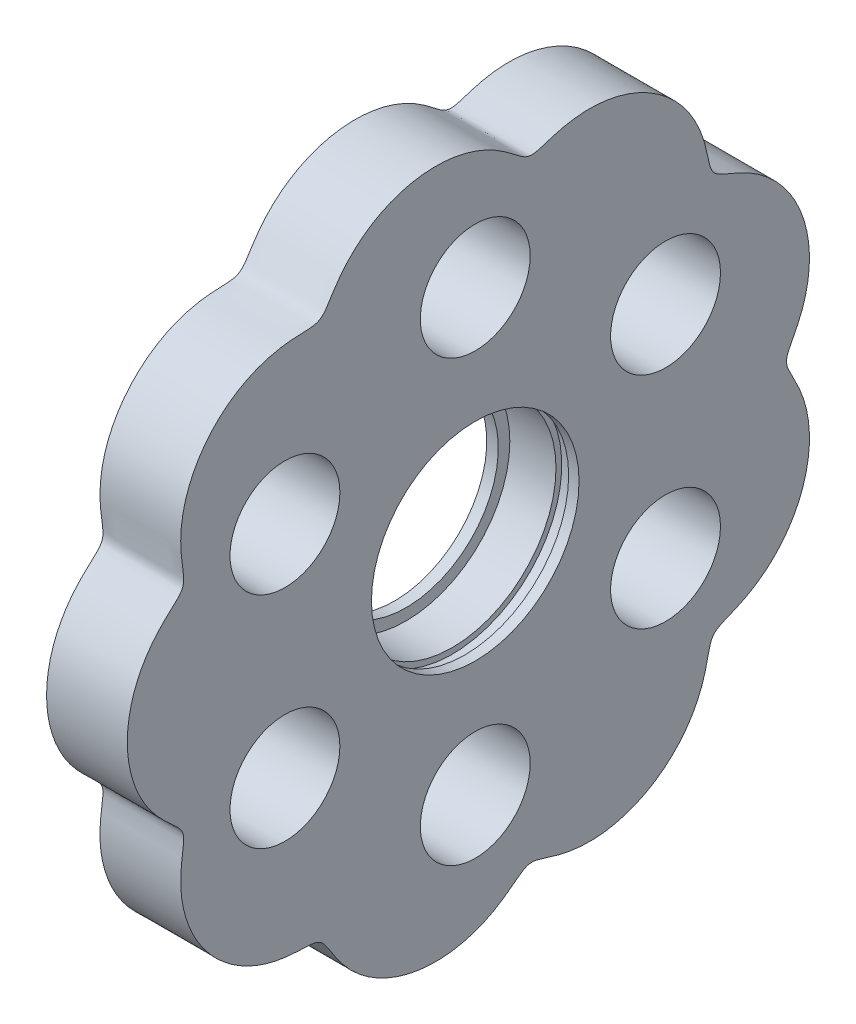
SolidWorks part; units mm, degrees
ref_plane "Front Plane" through (0, 0, 0) normal (0, 0, 1) x (1, 0, 0)
ref_plane "Top Plane" through (0, 0, 0) normal (0, 1, 0) x (1, 0, 0)
ref_plane "Right Plane" through (0, 0, 0) normal (1, 0, 0) x (0, 0, -1)
sketch "Sketch1" plane through (0, 0, 0) normal (1, 0, 0) x (0, 0, -1)
  circle A0 centre (0, 0) radius 9
  circle A1 centre (0, 0) radius 19.05 construction
  circle A2 centre (0, 19.05) radius 4.7625
  circle A3 centre (16.4978, 9.525) radius 4.7625
  circle A4 centre (16.4978, -9.525) radius 4.7625
  circle A5 centre (0, -19.05) radius 4.7625
  circle A6 centre (-16.4978, -9.525) radius 4.7625
  circle A7 centre (-16.4978, 9.525) radius 4.7625
  arc A8 (26.9875, 0) -> (26.994, 0.1287) centre (28.2671, 0) cw
  spline S0 degree 4 poles (24.0888, 15.5706) (24.4053, 15.3745) (25.0197, 14.9519) (25.8769, 14.2292) (26.8672, 13.1095) (27.6864, 11.8592) (28.3198, 10.5054) (28.7555, 9.0756) (28.9842, 7.5985) (28.9992, 6.1037) (28.7969, 4.6225) (28.4319, 3.3662) (27.9939, 2.3365) (27.6319, 1.6364) (27.4151, 1.2322) (27.2721, 0.9508) (27.1976, 0.7951) (27.1297, 0.6399) (27.0713, 0.4845) (27.0322, 0.3515) (27.009, 0.2424) (26.9965, 0.158) (26.9903, 0.0923) (26.9872, 0.0214) (26.9873, -0.0243) (26.9907, -0.0988) (26.9976, -0.1672) (27.0116, -0.2569) (27.033, -0.3527) (27.0616, -0.4505) (27.0986, -0.5565) (27.1336, -0.6462) (27.184, -0.7644) (27.252, -0.9101) (27.336, -1.0777) (27.4557, -1.3071) (27.5979, -1.5747) (27.8035, -1.97) (28.1452, -2.6757) (28.5405, -3.6809) (28.8775, -5.0165) (29.0228, -6.5839) (28.9282, -8.155) (28.602, -9.681) (28.0595, -11.1296) (27.3186, -12.4723) (26.3986, -13.6824) (25.3108, -14.7449) (24.0763, -15.6324) (22.9569, -16.2115) (22.0305, -16.5814) (21.3839, -16.8484) (21.04, -17.024) (20.7809, -17.218) (20.5918, -17.4348) (20.4481, -17.6972) (20.3419, -18.0072) (20.2297, -18.4621) (20.1126, -19.0338) (19.914, -19.899) (19.5509, -21.0362) (18.9588, -22.3) (18.0652, -23.6211) (16.9786, -24.7884) (15.741, -25.7664) (14.387, -26.5407) (12.9504, -27.1023) (11.4642, -27.4448) (9.9433, -27.5649) (8.4218, -27.4553) (7.1873, -27.1813) (6.2364, -26.8693) (5.5675, -26.6566) (5.1904, -26.5681) (4.8658, -26.547) (4.5781, -26.5886) (4.2474, -26.7152) (3.8366, -26.9833) (3.3422, -27.3762) (2.7495, -27.8328) (2.0842, -28.286) (1.2132, -28.7906) (0.1095, -29.2852) (-1.2457, -29.6877) (-2.8471, -29.9) (-4.4265, -29.864) (-5.9478, -29.6003) (-7.3813, -29.1318) (-8.7031, -28.4822) (-9.9193, -27.651) (-10.8676, -26.778) (-11.5836, -25.939) (-12.0909, -25.227) (-12.44, -24.6828) (-12.7368, -24.2034) (-12.9824, -23.8371) (-13.2161, -23.5701) (-13.4342, -23.3978) (-13.6702, -23.2745) (-14.0009, -23.1817) (-14.4257, -23.1396) (-14.975, -23.12) (-15.6229, -23.0959) (-16.5059, -23.0244) (-17.6152, -22.8368) (-18.8754, -22.461) (-20.2365, -21.8245) (-21.4907, -20.9972) (-22.6347, -19.9799) (-23.6367, -18.7847) (-24.4641, -17.4286) (-25.0837, -15.9347) (-25.4617, -14.3623) (-25.5708, -12.9509) (-25.5065, -11.7424) (-25.3804, -10.8005) (-25.2874, -10.175) (-25.2596, -9.6848) (-25.3141, -9.3347) (-25.4207, -9.0643) (-25.6003, -8.7933) (-25.8648, -8.5109) (-26.3827, -8.0382) (-27.1277, -7.3718) (-27.982, -6.4414) (-28.838, -5.1809) (-29.4952, -3.8061) (-29.9431, -2.3501) (-30.1773, -0.8262) (-30.1859, 0.7334) (-29.9601, 2.2957) (-29.4936, 3.8223) (-28.7978, 5.2598) (-27.8844, 6.5692) (-26.9944, 7.5041) (-26.2533, 8.1483) (-25.7691, 8.6082) (-25.554, 8.8559) (-25.397, 9.1107) (-25.3029, 9.3826) (-25.2632, 9.7035) (-25.2825, 10.0889) (-25.374, 10.7816) (-25.5173, 11.7677) (-25.5763, 13.0252) (-25.4267, 14.5364) (-25.0526, 16.0084) (-24.4671, 17.4093) (-23.6805, 18.7173) (-22.7082, 19.9035) (-21.5677, 20.9412) (-20.2801, 21.8031) (-18.8777, 22.4636) (-17.3913, 22.9024) (-16.1126, 23.0797) (-15.0844, 23.1155) (-14.3595, 23.1435) (-13.9557, 23.1908) (-13.6345, 23.2884) (-13.3798, 23.4308) (-13.1556, 23.6314) (-12.9492, 23.8869) (-12.5804, 24.4445) (-12.0739, 25.2868) (-11.3064, 26.3262) (-10.1733, 27.4532) (-8.8763, 28.3877) (-7.4517, 29.1112) (-5.951, 29.6032) (-4.4132, 29.8635) (-2.8725, 29.8956) (-1.3626, 29.7057) (0.1036, 29.2961) (1.4916, 28.6715) (2.5547, 27.9917) (3.3393, 27.3739) (3.8944, 26.9467) (4.2184, 26.7359) (4.5167, 26.6071) (4.8017, 26.5501) (5.1561, 26.5584) (5.6344, 26.6716) (6.2346, 26.8723) (6.9494, 27.0987) (7.7315, 27.2964) (8.7249, 27.4714) (9.934, 27.5567) (11.3479, 27.4681) (12.9278, 27.1153) (14.407, 26.5337) (15.757, 25.7527) (16.9557, 24.8017) (17.986, 23.7101) (18.847, 22.4805) (19.4343, 21.3054) (19.8105, 20.2463) (20.0336, 19.3898) (20.1695, 18.7566) (20.2843, 18.2196) (20.3998, 17.809) (20.5517, 17.4956) (20.7345, 17.262) (21.0076, 17.0389) (21.4443, 16.8166) (22.0311, 16.585) (22.7222, 16.3006) (23.4467, 15.952) (24.3186, 15.4512) (25.2985, 14.7445) (26.3245, 13.7743) (27.3096, 12.4964) (28.0876, 11.08) (28.6409, 9.5587) (28.9552, 7.968) (29.0115, 6.5478) (28.8998, 5.3367) (28.7005, 4.3444) (28.5064, 3.663) (28.3024, 3.0913) (28.0706, 2.5305) (27.8776, 2.1183) (27.6938, 1.758) (27.5289, 1.445) (27.4344, 1.2661) (27.3474, 1.0997) (27.2692, 0.9445) (27.2006, 0.8008) (27.1419, 0.6679) (27.0943, 0.547) (27.0609, 0.4471) (27.0392, 0.3712) (27.0263, 0.32) (27.0169, 0.2778) (27.0063, 0.2221) (26.9958, 0.1509) (26.991, 0.1035) (26.9863, 0.0082) (26.9882, -0.0616) (26.9948, -0.1466) (27.0074, -0.2355) (27.0276, -0.33) (27.0557, -0.4305) (27.0857, -0.521) (27.1377, -0.6595) (27.2184, -0.8429) (27.3309, -1.0692) (27.4729, -1.3393) (27.6704, -1.7121) (27.9155, -2.1918) (28.1879, -2.7884) (28.4595, -3.5119) (28.7312, -4.4391) (28.9435, -5.5805) (29.0209, -6.9348) (28.8774, -8.4783) (28.5081, -9.9836) (27.9223, -11.4186) (27.1321, -12.7521) (26.1529, -13.9539) (25.2912, -14.7345) (24.6685, -15.1927) (24.3465, -15.4056) knots 0 0 0 0 0 0.006514 0.01303 0.019546 0.026062 0.032577 0.039093 0.045609 0.052125 0.05864 0.065156 0.068414 0.071671 0.072426 0.073181 0.073936 0.074691 0.075388 0.076084 0.076359 0.076634 0.076909 0.077183 0.077474 0.077765 0.078056 0.078347 0.079094 0.079468 0.079841 0.08031 0.080779 0.081716 0.082653 0.08359 0.085305 0.087019 0.090448 0.097307 0.104164 0.111022 0.11788 0.124738 0.131364 0.137989 0.144616 0.151241 0.157866 0.164493 0.16659 0.168688 0.17011 0.171229 0.172221 0.173681 0.175312 0.176944 0.180417 0.183891 0.190839 0.197787 0.204734 0.211683 0.218631 0.225278 0.231925 0.238574 0.245221 0.251867 0.258517 0.260621 0.262725 0.264152 0.265274 0.266279 0.267774 0.270299 0.273819 0.277338 0.280856 0.284374 0.291412 0.298448 0.305486 0.312523 0.318944 0.325364 0.331785 0.338206 0.344627 0.347837 0.351047 0.353492 0.355937 0.357703 0.358757 0.359673 0.360776 0.362332 0.364727 0.367122 0.370397 0.373672 0.38022 0.386769 0.393319 0.399867 0.406416 0.413461 0.420507 0.427551 0.434596 0.441641 0.445164 0.448688 0.451216 0.452712 0.453718 0.454839 0.456265 0.458367 0.460468 0.46711 0.473749 0.480388 0.487029 0.493669 0.500309 0.507265 0.514221 0.521176 0.528131 0.535088 0.542043 0.543676 0.545309 0.546771 0.547764 0.548881 0.550302 0.552397 0.554492 0.561111 0.567729 0.574346 0.580965 0.587583 0.594201 0.600954 0.607708 0.614461 0.621213 0.627968 0.634721 0.636963 0.639205 0.640666 0.641809 0.642803 0.644267 0.645902 0.647536 0.654498 0.661461 0.668423 0.675385 0.682348 0.689311 0.695944 0.702577 0.709212 0.715844 0.722477 0.729112 0.731211 0.733311 0.734735 0.735855 0.736862 0.73836 0.740891 0.744417 0.747944 0.75147 0.754996 0.762047 0.769099 0.776151 0.783204 0.789746 0.796288 0.802831 0.809373 0.815915 0.819187 0.822458 0.824851 0.827244 0.828799 0.8299 0.830904 0.832398 0.83492 0.838435 0.84195 0.845465 0.848979 0.856009 0.863037 0.870067 0.877096 0.884172 0.891248 0.898323 0.901861 0.905399 0.908937 0.910706 0.912475 0.916013 0.916897 0.917782 0.918666 0.919551 0.920185 0.92082 0.921454 0.922089 0.922464 0.922652 0.92284 0.923028 0.923216 0.923591 0.923945 0.924298 0.924584 0.92487 0.925442 0.925859 0.926276 0.926694 0.927111 0.928446 0.92978 0.931115 0.93245 0.935827 0.939204 0.942582 0.945959 0.952715 0.95947 0.966225 0.97298 0.979735 0.986491 0.993246 1 1 1 1 1 construction
  spline S1 degree 4 poles (26.9875, 0) (26.9875, -0.0141) (26.9881, -0.0422) (26.9907, -0.0988) (26.9976, -0.1672) (27.0116, -0.2569) (27.033, -0.3527) (27.0616, -0.4505) (27.0986, -0.5565) (27.1336, -0.6462) (27.184, -0.7644) (27.252, -0.9101) (27.336, -1.0777) (27.4557, -1.3071) (27.5979, -1.5747) (27.8035, -1.97) (28.1452, -2.6757) (28.5405, -3.6809) (28.8775, -5.0165) (29.0228, -6.5839) (28.9282, -8.155) (28.602, -9.681) (28.0595, -11.1296) (27.3186, -12.4723) (26.3986, -13.6824) (25.3108, -14.7449) (24.0763, -15.6324) (22.9569, -16.2115) (22.0305, -16.5814) (21.3839, -16.8484) (21.04, -17.024) (20.7809, -17.218) (20.5918, -17.4348) (20.4481, -17.6972) (20.3419, -18.0072) (20.2297, -18.4621) (20.1126, -19.0338) (19.914, -19.899) (19.5509, -21.0362) (18.9588, -22.3) (18.0652, -23.6211) (16.9786, -24.7884) (15.741, -25.7664) (14.387, -26.5407) (12.9504, -27.1023) (11.4642, -27.4448) (9.9433, -27.5649) (8.4218, -27.4553) (7.1873, -27.1813) (6.2364, -26.8693) (5.5675, -26.6566) (5.1904, -26.5681) (4.8658, -26.547) (4.5781, -26.5886) (4.2474, -26.7152) (3.8366, -26.9833) (3.3422, -27.3762) (2.7495, -27.8328) (2.0842, -28.286) (1.2132, -28.7906) (0.1095, -29.2852) (-1.2457, -29.6877) (-2.8471, -29.9) (-4.4265, -29.864) (-5.9478, -29.6003) (-7.3813, -29.1318) (-8.7031, -28.4822) (-9.9193, -27.651) (-10.8676, -26.778) (-11.5836, -25.939) (-12.0909, -25.227) (-12.44, -24.6828) (-12.7368, -24.2034) (-12.9824, -23.8371) (-13.2161, -23.5701) (-13.4342, -23.3978) (-13.6702, -23.2745) (-14.0009, -23.1817) (-14.4257, -23.1396) (-14.975, -23.12) (-15.6229, -23.0959) (-16.5059, -23.0244) (-17.6152, -22.8368) (-18.8754, -22.461) (-20.2365, -21.8245) (-21.4907, -20.9972) (-22.6347, -19.9799) (-23.6367, -18.7847) (-24.4641, -17.4286) (-25.0837, -15.9347) (-25.4617, -14.3623) (-25.5708, -12.9509) (-25.5065, -11.7424) (-25.3804, -10.8005) (-25.2874, -10.175) (-25.2596, -9.6848) (-25.3141, -9.3347) (-25.4207, -9.0643) (-25.6003, -8.7933) (-25.8648, -8.5109) (-26.3827, -8.0382) (-27.1277, -7.3718) (-27.982, -6.4414) (-28.838, -5.1809) (-29.4952, -3.8061) (-29.9431, -2.3501) (-30.1773, -0.8262) (-30.1859, 0.7334) (-29.9601, 2.2957) (-29.4936, 3.8223) (-28.7978, 5.2598) (-27.8844, 6.5692) (-26.9944, 7.5041) (-26.2533, 8.1483) (-25.7691, 8.6082) (-25.554, 8.8559) (-25.397, 9.1107) (-25.3029, 9.3826) (-25.2632, 9.7035) (-25.2825, 10.0889) (-25.374, 10.7816) (-25.5173, 11.7677) (-25.5763, 13.0252) (-25.4267, 14.5364) (-25.0526, 16.0084) (-24.4671, 17.4093) (-23.6805, 18.7173) (-22.7082, 19.9035) (-21.5677, 20.9412) (-20.2801, 21.8031) (-18.8777, 22.4636) (-17.3913, 22.9024) (-16.1126, 23.0797) (-15.0844, 23.1155) (-14.3595, 23.1435) (-13.9557, 23.1908) (-13.6345, 23.2884) (-13.3798, 23.4308) (-13.1556, 23.6314) (-12.9492, 23.8869) (-12.5804, 24.4445) (-12.0739, 25.2868) (-11.3064, 26.3262) (-10.1733, 27.4532) (-8.8763, 28.3877) (-7.4517, 29.1112) (-5.951, 29.6032) (-4.4132, 29.8635) (-2.8725, 29.8956) (-1.3626, 29.7057) (0.1036, 29.2961) (1.4916, 28.6715) (2.5547, 27.9917) (3.3393, 27.3739) (3.8944, 26.9467) (4.2184, 26.7359) (4.5167, 26.6071) (4.8017, 26.5501) (5.1561, 26.5584) (5.6344, 26.6716) (6.2346, 26.8723) (6.9494, 27.0987) (7.7315, 27.2964) (8.7249, 27.4714) (9.934, 27.5567) (11.3479, 27.4681) (12.9278, 27.1153) (14.407, 26.5337) (15.757, 25.7527) (16.9557, 24.8017) (17.986, 23.7101) (18.847, 22.4805) (19.4343, 21.3054) (19.8105, 20.2463) (20.0336, 19.3898) (20.1695, 18.7566) (20.2843, 18.2196) (20.3998, 17.809) (20.5517, 17.4956) (20.7345, 17.262) (21.0076, 17.0389) (21.4443, 16.8166) (22.0311, 16.585) (22.7222, 16.3006) (23.4467, 15.952) (24.3186, 15.4512) (25.2985, 14.7445) (26.3245, 13.7743) (27.3096, 12.4964) (28.0876, 11.08) (28.6409, 9.5587) (28.9552, 7.968) (29.0115, 6.5478) (28.8998, 5.3367) (28.7005, 4.3444) (28.5064, 3.663) (28.3024, 3.0913) (28.0706, 2.5305) (27.8776, 2.1183) (27.6938, 1.758) (27.5289, 1.445) (27.4344, 1.2661) (27.3474, 1.0997) (27.2692, 0.9445) (27.2006, 0.8008) (27.1419, 0.6679) (27.0943, 0.547) (27.0609, 0.4471) (27.0392, 0.3712) (27.0263, 0.32) (27.0169, 0.2778) (27.0063, 0.2221) (26.9992, 0.1737) (26.9958, 0.1468) (26.994, 0.1287) knots 0.077183 0.077183 0.077183 0.077183 0.077183 0.077474 0.077765 0.078056 0.078347 0.079094 0.079468 0.079841 0.08031 0.080779 0.081716 0.082653 0.08359 0.085305 0.087019 0.090448 0.097307 0.104164 0.111022 0.11788 0.124738 0.131364 0.137989 0.144616 0.151241 0.157866 0.164493 0.16659 0.168688 0.17011 0.171229 0.172221 0.173681 0.175312 0.176944 0.180417 0.183891 0.190839 0.197787 0.204734 0.211683 0.218631 0.225278 0.231925 0.238574 0.245221 0.251867 0.258517 0.260621 0.262725 0.264152 0.265274 0.266279 0.267774 0.270299 0.273819 0.277338 0.280856 0.284374 0.291412 0.298448 0.305486 0.312523 0.318944 0.325364 0.331785 0.338206 0.344627 0.347837 0.351047 0.353492 0.355937 0.357703 0.358757 0.359673 0.360776 0.362332 0.364727 0.367122 0.370397 0.373672 0.38022 0.386769 0.393319 0.399867 0.406416 0.413461 0.420507 0.427551 0.434596 0.441641 0.445164 0.448688 0.451216 0.452712 0.453718 0.454839 0.456265 0.458367 0.460468 0.46711 0.473749 0.480388 0.487029 0.493669 0.500309 0.507265 0.514221 0.521176 0.528131 0.535088 0.542043 0.543676 0.545309 0.546771 0.547764 0.548881 0.550302 0.552397 0.554492 0.561111 0.567729 0.574346 0.580965 0.587583 0.594201 0.600954 0.607708 0.614461 0.621213 0.627968 0.634721 0.636963 0.639205 0.640666 0.641809 0.642803 0.644267 0.645902 0.647536 0.654498 0.661461 0.668423 0.675385 0.682348 0.689311 0.695944 0.702577 0.709212 0.715844 0.722477 0.729112 0.731211 0.733311 0.734735 0.735855 0.736862 0.73836 0.740891 0.744417 0.747944 0.75147 0.754996 0.762047 0.769099 0.776151 0.783204 0.789746 0.796288 0.802831 0.809373 0.815915 0.819187 0.822458 0.824851 0.827244 0.828799 0.8299 0.830904 0.832398 0.83492 0.838435 0.84195 0.845465 0.848979 0.856009 0.863037 0.870067 0.877096 0.884172 0.891248 0.898323 0.901861 0.905399 0.908937 0.910706 0.912475 0.916013 0.916897 0.917782 0.918666 0.919551 0.920185 0.92082 0.921454 0.922089 0.922464 0.922652 0.92284 0.923028 0.923216 0.923591 0.923591 0.923591 0.923591 0.923591
  point P18 (0, 0)
  dimension "D1" = 18
  dimension "D2" = 9.525
  dimension "D3" = 38.1
  dimension "D4" = 6
extrude "Boss-Extrude1" add sketch "Sketch1" along normal blind 7
sketch "Sketch2" plane through (0, 0, 0) normal (-1, 0, 0) x (0, 0, 1)
  circle A0 centre (0, 0) radius 8
  circle A1 centre (0, 0) radius 9 construction
  circle A2 centre (0, 0) radius 9
  dimension "D1" = 16
extrude "Boss-Extrude2" add sketch "Sketch2" against normal blind 1
sketch "Sketch3" plane through (0, 0, 0) normal (0, 0, 1) x (1, 0, 0)
  line L0 (7, -9) -> (7, 9) construction
  line L1 (7, -9) -> (7, 9)
  line L2 (1, -9) -> (1, 9) construction
  line L3 (6.1, 9) -> (5, 9)
  line L4 (6.1, 9) -> (6.1, 9.5)
  line L5 (6.1, 9.5) -> (5, 9.5)
  line L6 (5, 9) -> (5, 9.5)
  line L7 (1, -9) -> (1, 9)
  line L8 (0, 0) -> (11.371, 0) construction
  dimension "D1" = 1.1
  dimension "D2" = 4
  dimension "D3" = 0.5
revolve "Cut-Revolve1" cut sketch "Sketch3" angle 360 about L8 region at (5.55, 9.25, 0)
